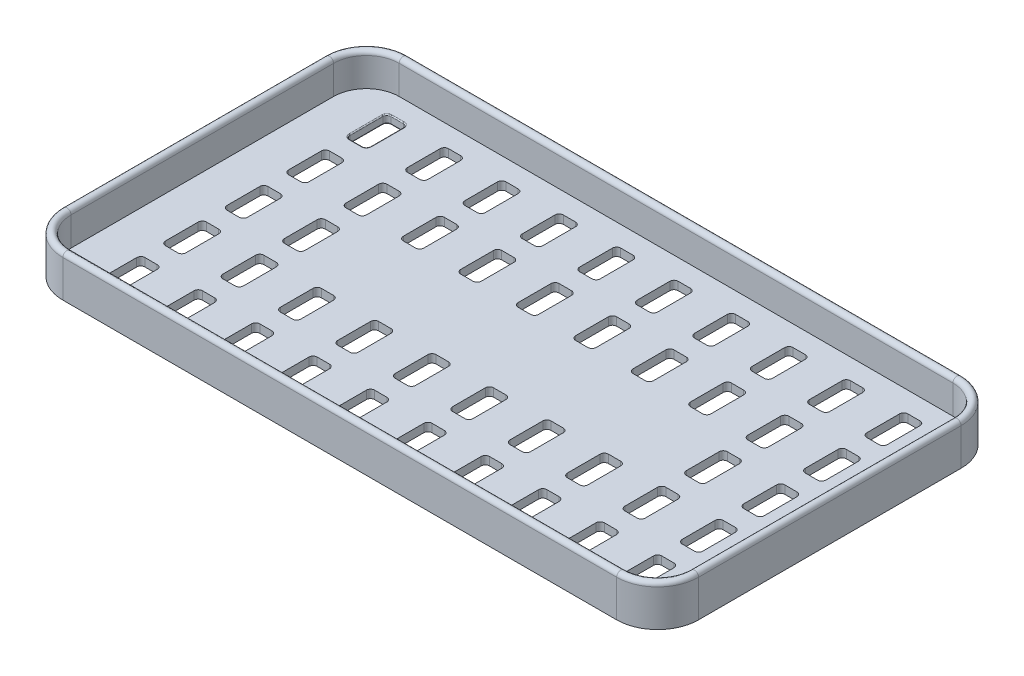
SolidWorks part; units mm, degrees
ref_plane "Front" through (0, 0, 0) normal (0, 0, 1) x (1, 0, 0)
ref_plane "Top" through (0, 0, 0) normal (0, 1, 0) x (1, 0, 0)
ref_plane "Right" through (0, 0, 0) normal (1, 0, 0) x (0, 0, -1)
sketch "Sketch1" plane through (0, 0, 0) normal (0, 1, 0) x (1, 0, 0)
  line L1 (-77.5, -42) -> (77.5, -42)
  line L2 (-77.5, -42) -> (-77.5, 42)
  line L3 (-77.5, 42) -> (77.5, 42)
  line L4 (77.5, -42) -> (77.5, 42)
  line L5 (-77.5, -42) -> (77.5, 42) construction
  line L6 (-77.5, 42) -> (77.5, -42) construction
  point P0 (0, 0)
  dimension "D1" = 155
  dimension "D2" = 84
extrude "Boss-Extrude1" add sketch "Sketch1" along normal blind 10
fillet "Fillet1" radius 10 4 edges at (-77.5, 5, 42) (-77.5, 5, -42) (77.5, 5, -42) (77.5, 5, 42)
shell "Shell1" thickness 2 removed face at (0, 10, 0)
sketch "Sketch2" plane through (0, 2, 0) normal (0, 1, 0) x (1, 0, 0)
  line L0 (67.5, 40) -> (-67.5, 40) construction
  line L1 (-65.5, 35) -> (-60.5, 35)
  line L2 (-65.5, 35) -> (-65.5, 25)
  line L3 (-65.5, 25) -> (-60.5, 25)
  line L4 (-60.5, 35) -> (-60.5, 25)
  line L5 (-65.5, 35) -> (-60.5, 25) construction
  line L6 (-65.5, 25) -> (-60.5, 35) construction
  line L7 (-75.5, 32) -> (-75.5, -32) construction
  point P0 (-63, 30)
  dimension "D1" = 10
  dimension "D2" = 12.5
  dimension "D3" = 10
  dimension "D4" = 5
extrude "Cut-Extrude1" cut sketch "Sketch2" against normal through all
fillet "Fillet2" radius 1 4 edges at (-60.5, 1, -25) (-65.5, 1, -25) (-65.5, 1, -35) (-60.5, 1, -35)
fillet "Fillet3" radius 0.25 16 edges at (-60.7929, 0, -34.7071) (-60.5, 0, -30) (-60.7929, 0, -25.2929) (-63, 0, -25) (-65.2071, 0, -25.2929) (-65.5, 0, -30) (-65.2071, 0, -34.7071) (-65.2071, 2, -34.7071) (-63, 2, -35) (-60.7929, 2, -34.7071) (-60.5, 2, -30) (-60.7929, 2, -25.2929) (-63, 2, -25) (-65.2071, 2, -25.2929) (-63, 0, -35) (-65.5, 2, -30)
fillet "Fillet4" 2 edges at (-77.5, 10, 0) (-75.5, 10, 0) type full round first side face at (-77.5, 5, 0) second side face at (-75.5, 6, 0) middle face at (0, 10, 0)
pattern_linear "LPattern1" count 10 spacing 14 along (1, 0, 0) count 5 spacing 15 along (0, 0, 1) skipping (2, 2), (3, 2), (4, 2), (5, 2), (6, 2), (7, 2) of "Cut-Extrude1", "Fillet2"
